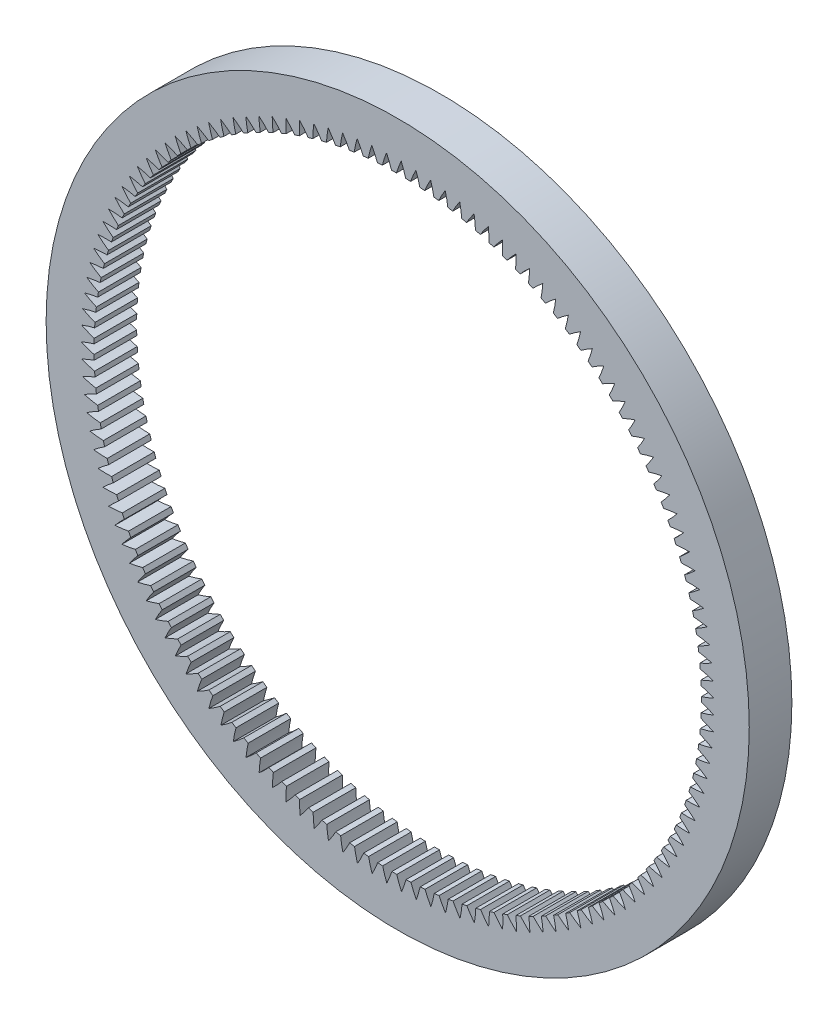
SolidWorks part; units mm, degrees
ref_plane "Front Plane" through (0, 0, 0) normal (0, 0, 1) x (1, 0, 0)
ref_plane "Top Plane" through (0, 0, 0) normal (0, 1, 0) x (1, 0, 0)
ref_plane "Right Plane" through (0, 0, 0) normal (1, 0, 0) x (0, 0, -1)
sketch "Sketch1" plane through (0, 0, 0) normal (0, 0, 1) x (1, 0, 0)
  line L0 (0, 0) -> (147.3511, 0.08) construction
  line L1 (0, 0) -> (147.3093, 3.5087) construction
  line L2 (0, 0) -> (147.3511, 0.08) construction
  line L3 (0, 0) -> (147.3402, 1.7945) construction
  line L4 (0, 0) -> (147.1878, 6.9355) construction
  line L5 (139.1603, 0.0756) -> (165, 0.0896)
  line L6 (0, 0) -> (367.0352, 8.7423)
  circle A0 centre (0, 0) radius 145.2 construction
  circle A1 centre (0, 0) radius 142.5111 construction
  circle A2 centre (0, 0) radius 136.4434 construction
  circle A3 centre (0, 0) radius 147.3511 construction
  arc A4 (142.4537, 4.044) -> (142.033, -11.6634) centre (0, 0) cw
  arc A5 (165, 0.0896) -> (164.4344, 13.6498) centre (0, 0) ccw
  spline S0 degree 4 poles (136.4434, 0) (136.5335, 0.002) (136.7135, 0.0093) (137.073, 0.0369) (137.5928, 0.0957) (138.1822, 0.1821) (139.0002, 0.3273) (140.0846, 0.5578) (141.4452, 0.9053) (143.7891, 1.6169) (146.9829, 2.8181) (151.3105, 4.8194) (156.6199, 7.8706) (162.1477, 11.7054) (167.7493, 16.311) (172.9989, 21.312) (177.9031, 26.6511) (182.6939, 32.5604) (188.165, 40.2289) (193.9819, 49.8453) (199.7515, 61.5574) (204.2979, 73.4098) (207.4637, 83.8128) (210.0618, 94.3676) (211.7634, 103.2675) (213.0154, 112.2411) (213.8316, 121.262) (214.2285, 128.4973) (214.4113, 137.553) (214.1398, 148.4214) (213.1304, 161.0679) (211.4543, 172.7284) (209.7578, 181.6258) (208.4833, 187.3734) (207.863, 190.0168) (207.3232, 192.2191) (206.8814, 193.9675) (206.4612, 195.5785) (206.0841, 196.9907) (205.722, 198.313) (205.4337, 199.3518) (205.0443, 200.723) (204.762, 201.7004) (204.2931, 203.2978) (203.9206, 204.5289) (203.4624, 206.027) (203.0426, 207.3617) (202.5874, 208.7889) (202.1398, 210.1598) (201.5609, 211.9038) (200.8558, 213.9726) (200.0069, 216.3909) (199.1334, 218.7914) (198.3642, 220.847) (197.8421, 222.2106) (197.5781, 222.8931) (197.4457, 223.2333) knots 0 0 0 0 0 0.001401 0.002802 0.005604 0.008133 0.010661 0.015718 0.022839 0.02996 0.048734 0.068727 0.096889 0.125051 0.153212 0.181374 0.209535 0.237696 0.271429 0.327752 0.384075 0.440398 0.46856 0.496721 0.553044 0.581206 0.609367 0.637529 0.66569 0.722013 0.778336 0.834659 0.84874 0.86282 0.869861 0.876901 0.883942 0.890982 0.895509 0.900036 0.904564 0.909091 0.914773 0.920455 0.926136 0.931818 0.9375 0.943182 0.948864 0.954545 0.965909 0.977273 0.988636 0.994318 1 1 1 1 1 construction
  spline S1 degree 4 poles (136.4434, 0) (136.5335, 0.002) (136.7135, 0.0093) (137.073, 0.0369) (137.5928, 0.0957) (138.1822, 0.1821) (139.0002, 0.3273) (140.0846, 0.5578) (141.4452, 0.9053) (143.7891, 1.6169) (146.9829, 2.8181) (151.3105, 4.8194) (156.6199, 7.8706) (162.1477, 11.7054) (167.7493, 16.311) (172.9989, 21.312) (177.9031, 26.6511) (182.6939, 32.5604) (188.165, 40.2289) (193.9819, 49.8453) (199.7515, 61.5574) (204.2979, 73.4098) (207.4637, 83.8128) (210.0618, 94.3676) (211.7634, 103.2675) (213.0154, 112.2411) (213.8316, 121.262) (214.2285, 128.4973) (214.4113, 137.553) (214.1398, 148.4214) (213.1304, 161.0679) (211.4543, 172.7284) (209.7578, 181.6258) (208.4833, 187.3734) (207.863, 190.0168) (207.3232, 192.2191) (206.8814, 193.9675) (206.4612, 195.5785) (206.0841, 196.9907) (205.722, 198.313) (205.4337, 199.3518) (205.1592, 200.3186) (205.0117, 200.8334) (204.9383, 201.0877) knots 0 0 0 0 0 0.001401 0.002802 0.005604 0.008133 0.010661 0.015718 0.022839 0.02996 0.048734 0.068727 0.096889 0.125051 0.153212 0.181374 0.209535 0.237696 0.271429 0.327752 0.384075 0.440398 0.46856 0.496721 0.553044 0.581206 0.609367 0.637529 0.66569 0.722013 0.778336 0.834659 0.84874 0.86282 0.869861 0.876901 0.883942 0.890982 0.895509 0.900036 0.904564 0.909091 0.909091 0.909091 0.909091 0.909091
  point P14 (136.4333, 1.6616)
  point P20 (142.5058, 1.2356)
  point P21 (142.5005, 1.7355)
  point P22 (139.2781, -0.6087)
  point P23 (142.5058, 1.6657)
  point P24 (142.4933, 1.2356)
  dimension "pitchRadius" = 145.2
  dimension "addendumRadius" = 147.3511
  dimension "dedendumRadius" = 142.5111
  dimension "baseRadius" = 136.4434
  dimension "D1" = 1.333
  dimension "D2" = 0.667
  dimension "toothArc" = 2.667
  dimension "D3" = 165
  dimension "backlash" = 0.5
extrude "Boss-Extrude1" add sketch "Sketch1" along normal blind 20 contours S1 L5 A5 L6 region at (154.9006, 1.7989, 0)
mirror "Mirror1" about plane through (0, 0, 20) normal (-0.0238, 0.9997, 0) of "Boss-Extrude1"
pattern_circular "CirPattern6" count 135 over 360 about axis through (0, 0, 20) along (0, 0, -1) of "Boss-Extrude1", "Mirror1"
equation "\"D1@Sketch1\"=\"toothArc@Sketch1\"/2"
equation "\"D2@Sketch1\"=\"toothArc@Sketch1\"/4"
equation "\"pitchRadius\"= 14.52"
equation "\"nTeeth\"= 135"
equation "\"pressureAngle\"= 20"
equation "\"baseRadius\"= \"pitchRadius\" * cos ( \"pressureAngle\" )"
equation "\"diametralPitch\"= \"nTeeth\" / ( 2 * \"pitchRadius\" )'note units: cm^-1"
equation "\"dedendum\"= 1.25 / \"diametralPitch\"'for full depth, 20 deg pressure angle"
equation "\"addendum\"= 1 / \"diametralPitch\""
equation "\"pitchRadius@Sketch1\"= \"pitchRadius\""
equation "\"addendumRadius@Sketch1\"= \"pitchRadius\" + \"addendum\""
equation "\"dedendumRadius@Sketch1\"= \"pitchRadius\" - \"dedendum\""
equation "\"baseRadius@Sketch1\"= \"baseRadius\""
equation "\"toothArc@Sketch1\"=360/\"nTeeth\""
equation "\"D1@CirPattern1\"=\"nTeeth\""
